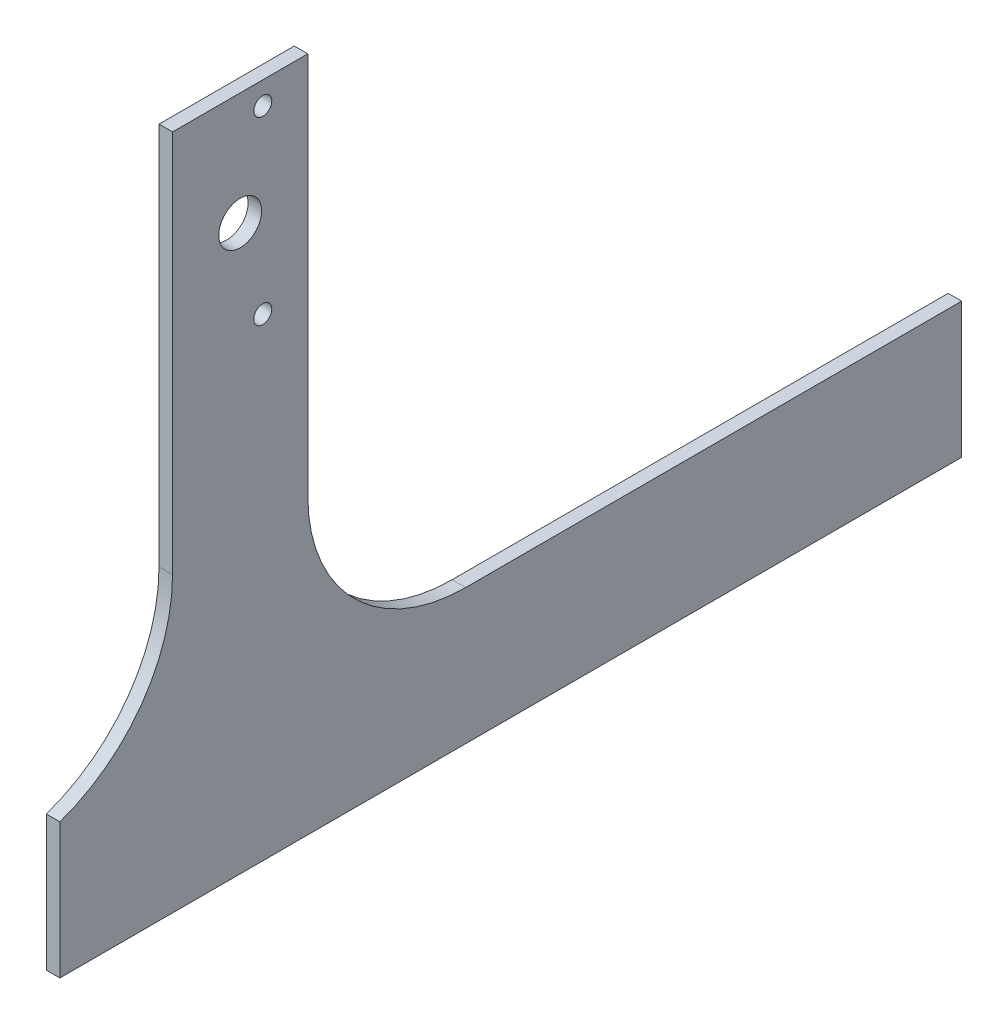
SolidWorks part; units mm, degrees
ref_plane "Front Plane" through (0, 0, 0) normal (0, 0, 1) x (1, 0, 0)
ref_plane "Top Plane" through (0, 0, 0) normal (0, 1, 0) x (1, 0, 0)
ref_plane "Right Plane" through (0, 0, 0) normal (1, 0, 0) x (0, 0, -1)
sketch "Sketch1" plane through (0, 0, 0) normal (1, 0, 0) x (0, 0, -1)
  line L0 (-1000, 0) -> (49000, 0) construction
  line L1 (-80, -250) -> (320, -250)
  line L6 (-900, -190) -> (49100, -190) construction
  line L7 (0, -1000) -> (0, 49000) construction
  line L10 (-80, -190) -> (-80, -250)
  line L11 (-30, 50) -> (-30, -120.0496)
  line L12 (84.8849, -120.0496) -> (-119.1387, -120.0496) construction
  line L20 (0, -750) -> (0, 49250) construction
  line L30 (320, -190) -> (320, -250)
  line L31 (30, 50) -> (30, -120)
  line L32 (-30, 50) -> (30, 50)
  line L33 (100, -190) -> (320, -190)
  line L34 (-27.1942, 0) -> (27.1942, 0) construction
  line L39 (10, -950) -> (10, 49050) construction
  circle A1 centre (0, 0) radius 4
  circle A2 centre (10, -40) radius 4
  circle A3 centre (10, 40) radius 4
  arc A5 (100, -190) -> (30, -120) centre (100, -120) cw
  arc A8 (-80, -190) -> (-30, -120.0496) centre (-103.9305, -120.0496) ccw
  point P0 (0, 0)
  point P1 (0, 0)
  point P51 (0, 0)
  dimension "D7" = 73.9305
  dimension "D14" = 8
  dimension "D16" = 40
  dimension "D18" = 120
  dimension "D12" = 70
  dimension "D6" = 10
  dimension "D2" = 400
  dimension "D3" = 50
  dimension "D4" = 60
  dimension "D5" = 250
  dimension "D8" = 300
  dimension "D9" = 70
  dimension "D11" = 60
  dimension "D15" = 50
  dimension "D17" = 40
extrude "Boss-Extrude1" add sketch "Sketch1" along normal blind 6
sketch "Sketch3" plane through (6, 0, 0) normal (1, 0, 0) x (0, 0, -1)
  circle A0 centre (0, 0) radius 9.5
  dimension "D1" = 19
extrude "Cut-Extrude1" cut sketch "Sketch3" against normal up to next
